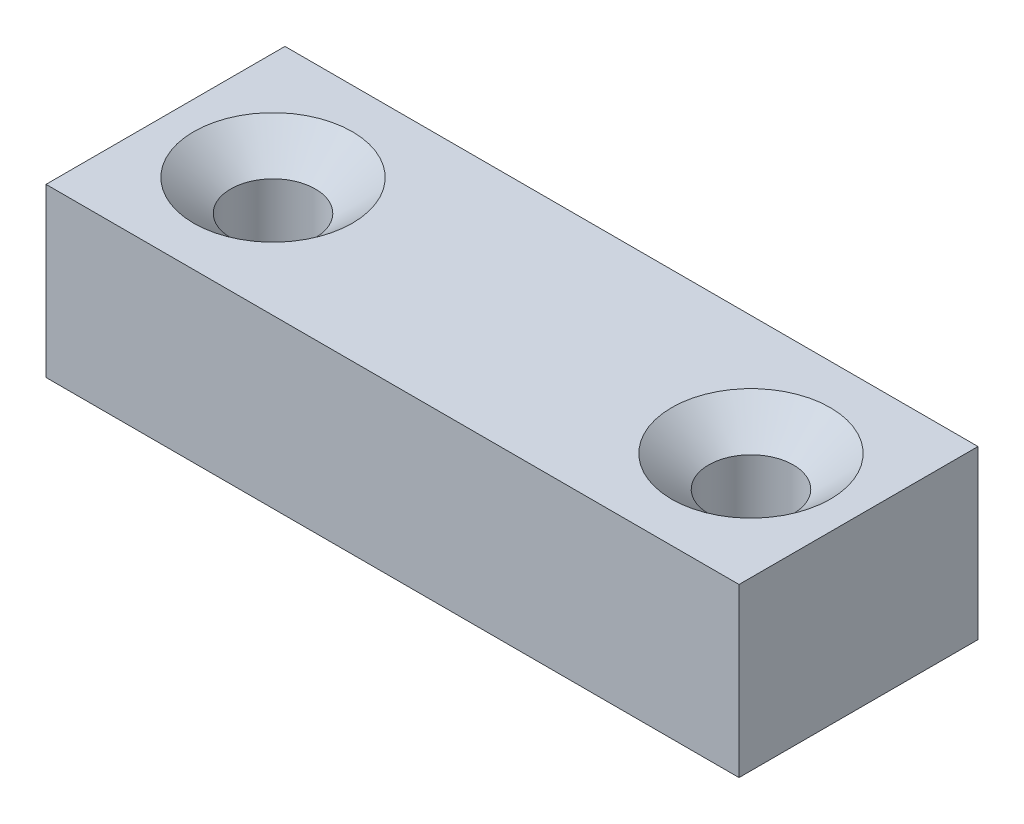
SolidWorks part; units mm, degrees
ref_plane "Front Plane" through (0, 0, 0) normal (0, 0, 1) x (1, 0, 0)
ref_plane "Top Plane" through (0, 0, 0) normal (0, 1, 0) x (1, 0, 0)
ref_plane "Right Plane" through (0, 0, 0) normal (1, 0, 0) x (0, 0, -1)
sketch "Sketch1" plane through (0, 0, 0) normal (0, 1, 0) x (1, 0, 0)
  line L1 (0, 0) -> (36.83, 0)
  line L2 (0, 0) -> (0, -12.7)
  line L3 (0, -12.7) -> (36.83, -12.7)
  line L4 (36.83, 0) -> (36.83, -12.7)
  point P9 (18.415, 0)
  point P10 (0, -6.35)
  dimension "D1" = 36.83
  dimension "D2" = 12.7
extrude "Boss-Extrude1" add sketch "Sketch1" along normal blind 8.89
hole_wizard "CSK for #8 Flat Head Machine Screw (100)1" positions "Sketch3" profile "Sketch2" countersink size "#8" standard "ANSI Inch" end condition through all
sketch "Sketch3" plane through (0, 8.89, 0) normal (0, 1, 0) x (1, 0, 0)
  line L0 (36.83, 0) -> (0, 0) construction
  line L1 (0, 0) -> (0, -12.7) construction
  point P0 (5.715, -6.35)
  point P2 (31.115, -6.35)
  point P5 (18.415, 0)
  point P8 (0, -6.35)
  dimension "D1" = 25.4
  dimension "D2" = 12.7
  dimension "D3" = 0
  dimension "D4" = 0
sketch "Sketch2" plane through (5.715, 8.89, 6.35) normal (1, 0, 0) x (0, 0, 1)
  line L0 (0, 0) -> (0, 8.89)
  line L1 (0, 8.89) -> (2.2479, 8.89)
  line L2 (2.2479, 8.89) -> (2.2479, 1.6518)
  line L3 (2.2479, 1.6518) -> (4.2164, 0)
  line L5 (4.2164, 0) -> (0, 0)
  line L6 (-2.2479, 1.6518) -> (-4.2164, 0) construction
  line L11 (0, -6.35) -> (0, 107.95) construction
  dimension "Thru Hole Dia." = 4.4958
  dimension "Thru Hole Depth" = 8.89
  dimension "Near C'Sink Dia." = 8.4328
  dimension "Near C'Sink Angle" = 100
